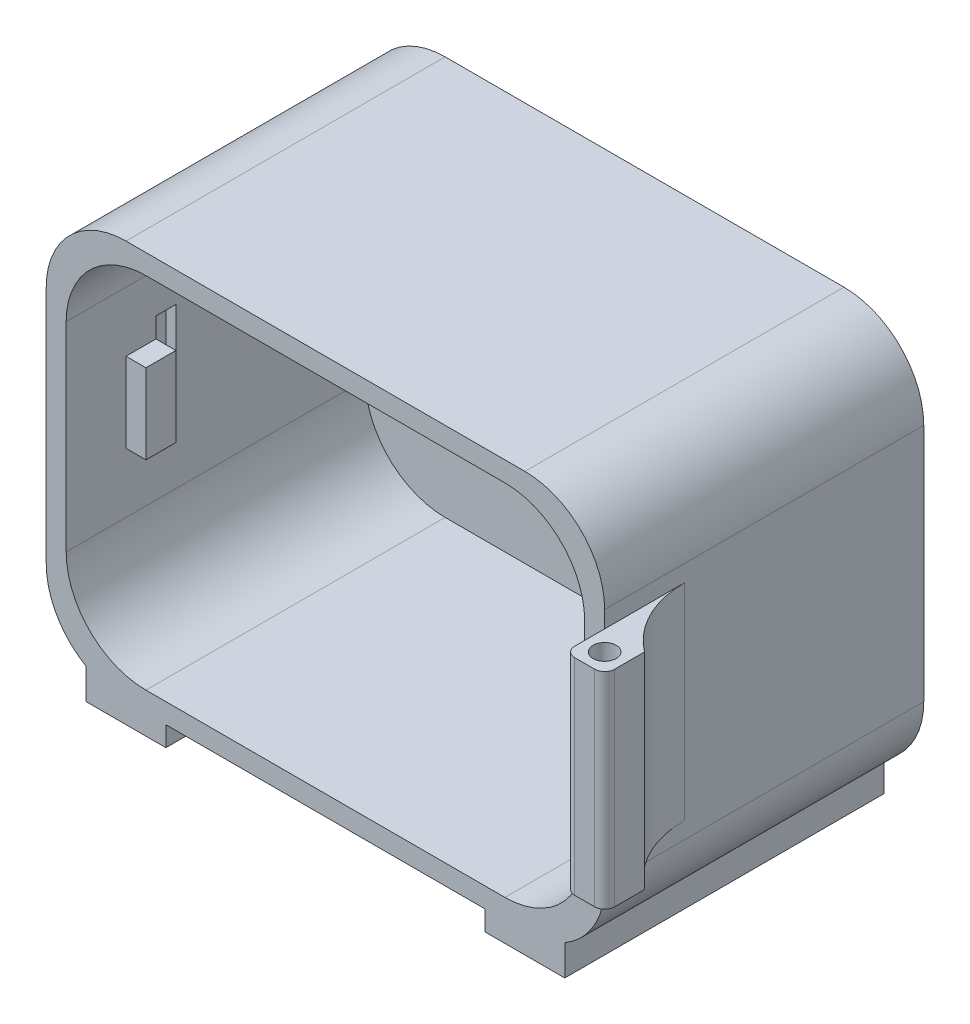
SolidWorks part; units mm, degrees
ref_plane "Front Plane" through (0, 0, 0) normal (0, 0, 1) x (1, 0, 0)
ref_plane "Top Plane" through (0, 0, 0) normal (0, 1, 0) x (1, 0, 0)
ref_plane "Right Plane" through (0, 0, 0) normal (1, 0, 0) x (0, 0, -1)
sketch "Sketch1" plane through (0, 0, 0) normal (0, 0, 1) x (1, 0, 0)
  line L0 (-82.55, 31.75) -> (-82.55, -31.75)
  line L1 (-63.5, 63.5) -> (63.5, 63.5)
  line L2 (-88.9, 38.1) -> (-88.9, -38.1)
  line L3 (-63.5, -63.5) -> (63.5, -63.5)
  line L4 (88.9, 38.1) -> (88.9, -38.1)
  line L5 (-88.9, 63.5) -> (88.9, -63.5) construction
  line L6 (-88.9, -63.5) -> (88.9, 63.5) construction
  line L7 (-57.15, -57.15) -> (57.15, -57.15)
  line L8 (82.55, 31.75) -> (82.55, -31.75)
  line L9 (-57.15, 57.15) -> (57.15, 57.15)
  line L10 (-88.9, 63.5) -> (88.9, 63.5) construction
  line L11 (88.9, 63.5) -> (88.9, -63.5) construction
  line L12 (82.55, 57.15) -> (82.55, -57.15) construction
  line L13 (-82.55, 57.15) -> (82.55, 57.15) construction
  line L14 (-82.55, -57.15) -> (82.55, -57.15) construction
  line L15 (-88.9, -63.5) -> (88.9, -63.5) construction
  line L16 (-82.55, 57.15) -> (-82.55, -57.15) construction
  line L17 (-88.9, 63.5) -> (-88.9, -63.5) construction
  arc A0 (63.5, 63.5) -> (88.9, 38.1) centre (63.5, 38.1) cw
  arc A1 (82.55, 31.75) -> (57.15, 57.15) centre (57.15, 31.75) ccw
  arc A2 (57.15, -57.15) -> (82.55, -31.75) centre (57.15, -31.75) ccw
  arc A3 (63.5, -63.5) -> (88.9, -38.1) centre (63.5, -38.1) ccw
  arc A4 (-82.55, -31.75) -> (-57.15, -57.15) centre (-57.15, -31.75) ccw
  arc A5 (-88.9, -38.1) -> (-63.5, -63.5) centre (-63.5, -38.1) ccw
  arc A6 (-63.5, 63.5) -> (-88.9, 38.1) centre (-63.5, 38.1) ccw
  arc A7 (-82.55, 31.75) -> (-57.15, 57.15) centre (-57.15, 31.75) cw
  point P0 (0, 0)
  dimension "D4" = 25.4
  dimension "D1" = 177.8
  dimension "D2" = 127
  dimension "D3" = 6.35
extrude "Boss-Extrude1" add sketch "Sketch1" against normal blind 95.25
sketch "Sketch2" plane through (0, 0, -95.25) normal (0, 0, -1) x (-1, 0, 0)
  line L0 (-63.5, 63.5) -> (63.5, 63.5)
  line L1 (-63.5, 63.5) -> (63.5, 63.5) construction
  line L2 (0, 63.5) -> (0, -63.5) construction
  line L3 (63.5, -63.5) -> (-63.5, -63.5) construction
  line L4 (63.5, -63.5) -> (-63.5, -63.5)
  line L5 (-88.9, -38.1) -> (-88.9, 38.1) construction
  line L6 (-88.9, -38.1) -> (-88.9, 38.1)
  line L7 (88.9, -38.1) -> (88.9, 38.1)
  arc A0 (-88.9, 38.1) -> (-63.5, 63.5) centre (-63.5, 38.1) cw
  arc A1 (-63.5, -63.5) -> (-88.9, -38.1) centre (-63.5, -38.1) cw
  arc A2 (-88.9, -38.1) -> (-63.5, -63.5) centre (-63.5, -38.1) ccw construction
  arc A3 (63.5, -63.5) -> (88.9, -38.1) centre (63.5, -38.1) ccw
  arc A4 (88.9, 38.1) -> (63.5, 63.5) centre (63.5, 38.1) ccw
extrude "Boss-Extrude2" add sketch "Sketch2" along normal blind 6.35
sketch "Sketch4" plane through (0, -63.5, 0) normal (0, -1, 0) x (1, 0, 0)
  line L0 (-76.2, 0) -> (-50.8, 0)
  line L2 (-76.2, 0) -> (-76.2, -101.6)
  line L3 (-88.9, -101.6) -> (-63.5, -101.6) construction
  line L4 (-76.2, -101.6) -> (-50.8, -101.6)
  line L5 (63.5, -101.6) -> (-63.5, -101.6) construction
  line L6 (-50.8, -101.6) -> (-50.8, 0)
  line L7 (0, 0) -> (0, -101.6) construction
  line L8 (-63.5, 0) -> (63.5, 0) construction
  line L9 (76.2, -101.6) -> (50.8, -101.6)
  line L10 (76.2, 0) -> (76.2, -101.6)
  line L11 (76.2, 0) -> (50.8, 0)
  line L12 (50.8, -101.6) -> (50.8, 0)
  point P4 (-63.5, 0)
  dimension "D1" = 25.4
extrude "Boss-Extrude3" add sketch "Sketch4" along normal blind 6.35 and the other way up to next
sketch "Sketch5" plane through (0, 0, 0) normal (0, 1, 0) x (1, 0, 0)
  line L0 (0, 0) -> (88.9, 0) construction
  line L1 (63.5, 0) -> (-63.5, 0) construction
  line L2 (95.25, 0) -> (101.6, 0) construction
  line L3 (88.9, 25.4) -> (88.9, 0)
  line L4 (95.25, 0) -> (95.25, -6.35) construction
  line L7 (101.6, -12.7) -> (88.9, -12.7)
  line L8 (101.6, -12.7) -> (101.6, 0)
  line L9 (101.6, 0) -> (95.25, 0)
  line L10 (88.9, -12.7) -> (88.9, 0)
  line L11 (101.6, -12.7) -> (88.9, 0) construction
  line L12 (101.6, 0) -> (88.9, -12.7) construction
  line L13 (88.9, -6.35) -> (101.6, -6.35) construction
  arc A3 (101.6, 0) -> (88.9, 25.4) centre (120.65, 25.4) cw
  circle A4 centre (95.25, -6.35) radius 3.675
  point P4 (98.425, 0)
  dimension "D2" = 7.35
  dimension "D1" = 6.35
  dimension "D3" = 88.9
  dimension "D4" = 25.4
extrude "Boss-Extrude5" add sketch "Sketch5" along normal blind 32.766 and the other way blind 32.766 contours A3 L3 L10 L7 L8 A4 region at (94.0273, 0, 0.7656)
fillet "Fillet1" radius 3.175 1 edges at (101.6, 0, 12.7)
sketch "Sketch6" plane through (0, 32.766, 0) normal (0, 1, 0) x (1, 0, 0)
  line L0 (91.575, -6.35) -> (88.9, -6.35) construction
  line L1 (88.9, 0) -> (88.9, -12.7) construction
  line L2 (97.1007, -9.525) -> (101.6, -9.525) construction
  circle A0 centre (95.25, -6.35) radius 3.675 construction
sketch "Sketch8" plane through (-82.55, 0, 0) normal (1, 0, 0) x (0, 0, -1)
  line L0 (0, -19.05) -> (28.575, -19.05) construction
  line L1 (0, 31.75) -> (0, -31.75) construction
  line L2 (28.575, -19.05) -> (34.925, -19.05)
  line L3 (34.925, -19.05) -> (34.925, 19.05)
  line L4 (34.925, 19.05) -> (28.575, 19.05)
  line L5 (28.575, 19.05) -> (28.575, -19.05)
  line L6 (95.25, -57.15) -> (0, -57.15) construction
  dimension "D1" = 28.575
  dimension "D2" = 6.35
  dimension "D3" = 38.1
  dimension "D4" = 38.1
extrude "Cut-Extrude1" cut sketch "Sketch8" against normal blind 3.175
sketch "Sketch10" plane through (-82.55, 0, 0) normal (1, 0, 0) x (0, 0, -1)
  line L0 (28.575, 0) -> (28.575, 12.7) construction
  line L1 (28.575, 19.05) -> (28.575, -19.05) construction
  line L3 (28.575, 12.7) -> (19.05, 12.7)
  line L4 (28.575, 12.7) -> (28.575, -12.7)
  line L5 (28.575, -12.7) -> (19.05, -12.7)
  line L6 (19.05, 12.7) -> (19.05, -12.7)
  point P7 (28.575, 0)
  dimension "D1" = 12.7
  dimension "D2" = 9.525
extrude "Boss-Extrude6" add sketch "Sketch10" along normal blind 6.35
sketch "Sketch11" plane through (0, 0, -101.6) normal (0, 0, -1) x (-1, 0, 0)
  line L0 (32.462, -188.0741) -> (352.462, -188.0741) construction
  line L1 (-8.558, 38.2776) -> (9.4147, 38.2776)
  line L2 (9.4147, 38.2776) -> (12.3761, 30.5166)
  line L3 (12.3761, 30.5166) -> (6.5554, 30.5166)
  line L4 (-8.558, 38.2776) -> (-26.541, -14.1457)
  line L5 (-26.541, -14.1457) -> (-20.9531, -14.1457)
  line L6 (-20.9531, -17.5278) -> (-27.8644, -17.5278)
  line L7 (-27.8644, -17.5278) -> (-30.0702, -24.7333)
  line L8 (-30.0702, -24.7333) -> (-9.6303, -24.7333)
  line L9 (-9.6303, -24.7333) -> (-7.4245, -17.5278)
  line L10 (-7.4245, -17.5278) -> (8.4569, -17.5278)
  line L11 (8.4569, -17.5278) -> (10.5156, -24.7333)
  line L12 (10.5156, -24.7333) -> (12.3761, -24.7333)
  line L13 (12.3761, -24.7333) -> (12.3761, -18.8513)
  line L14 (16.1034, -18.8513) -> (16.1034, -24.7333)
  line L15 (16.1034, -24.7333) -> (21.2502, -24.7333)
  line L16 (21.2502, -24.7333) -> (21.2502, -18.8513)
  line L17 (24.3382, -18.8513) -> (24.3382, -24.7333)
  line L18 (24.3382, -24.7333) -> (31.2496, -24.7333)
  line L19 (31.2496, -24.7333) -> (13.3095, 27.1753)
  line L20 (13.3095, 27.1753) -> (6.5554, 27.1753)
  line L21 (0.7548, 15.0295) -> (-4.8523, -6.6891)
  line L22 (-4.8523, -6.6891) -> (6.0184, -6.6891)
  line L23 (6.0184, -6.6891) -> (0.7548, 15.0295)
  arc A0 (6.5554, 30.5166) -> (6.5554, 27.1753) centre (2.9252, 28.8459) ccw
  arc A1 (12.3761, -18.8513) -> (16.1034, -18.8513) centre (14.2398, -15.2135) cw
  arc A2 (-20.9531, -14.1457) -> (-20.9531, -17.5278) centre (-17.0513, -15.8368) cw
  arc A3 (21.2502, -18.8513) -> (24.3382, -18.8513) centre (22.7942, -15.1977) cw
  circle A4 centre (2.9252, 28.8459) radius 1.6706
  circle A5 centre (-17.0513, -15.8368) radius 2.045
  circle A6 centre (14.2398, -15.2135) radius 2.3144
  circle A7 centre (22.7942, -15.1977) radius 1.5563
  circle A8 centre (0, 3.175) radius 44.8241
  point P39 (0.8064, 15.13)
  point P41 (-4.8655, -6.7402)
  point P42 (6.0184, -6.6891)
  point P43 (0, 15.1186)
  point P44 (0.7548, 15.0295)
  point P45 (0, 0)
  point P46 (0, 2.7081)
  dimension "D1" = 3.175
extrude "Cut-Extrude4" cut sketch "Sketch11" against normal blind 1.5875 contours A8 | L22 L23 L21 | A3 L17 L18 L19 L20 A0 L3 L2 L1 L4 L5 A2 L6 L7 L8 L9 L10 L11 L12 L13 A1 L14 L15 L16
sketch "Sketch12" plane through (0, 0, -101.6) normal (0, 0, -1) x (-1, 0, 0)
  line L0 (0, 0) -> (0, -57.15) construction
  line L1 (63.5, -57.15) -> (-63.5, -57.15) construction
  text T0 "amp-lab.org" font "Century Gothic" height in points 48
  point P6 (0, -57.15)
  dimension "D1" = 57.15
  dimension "D2" = 127
extrude "Cut-Extrude5" cut sketch "Sketch12" against normal blind 1.5875
fillet "Fillet2" radius 3.175 1 edges at (88.9, 0, 12.7)
